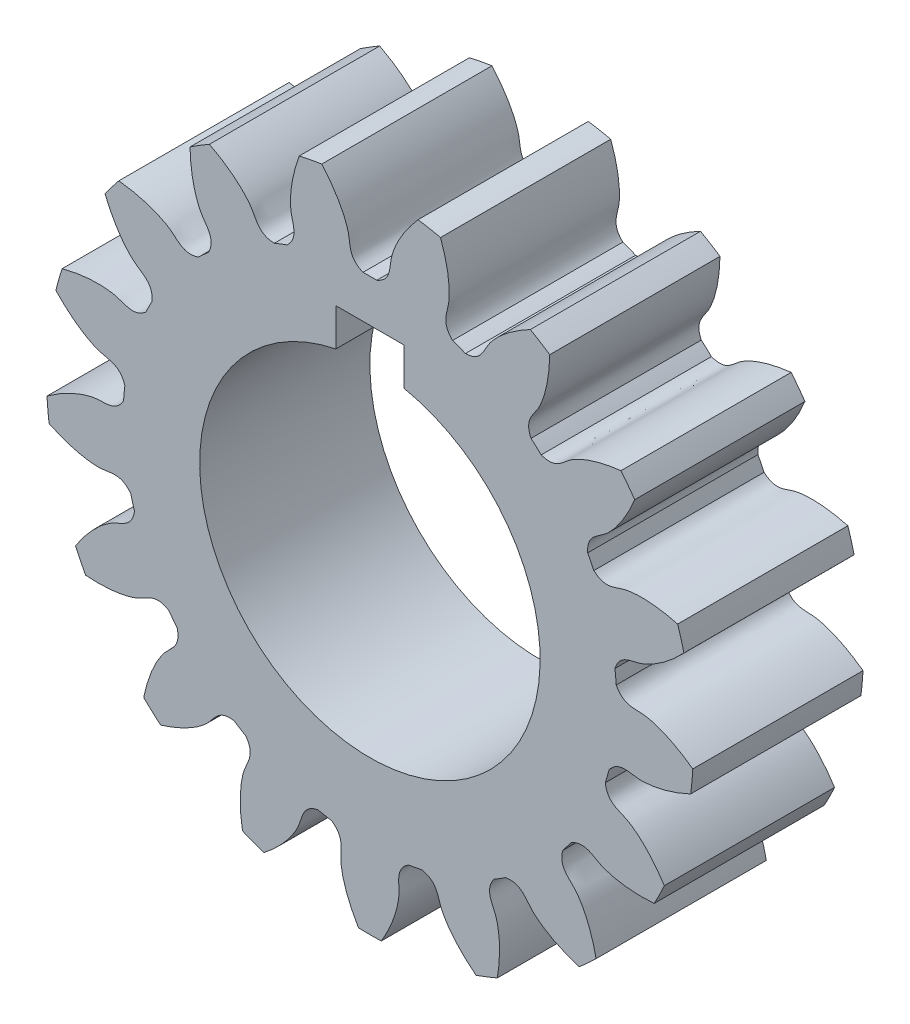
SolidWorks part; units mm, degrees
ref_plane "前视基准面" through (0, 0, 0) normal (0, 0, 1) x (1, 0, 0)
ref_plane "上视基准面" through (0, 0, 0) normal (0, 1, 0) x (1, 0, 0)
ref_plane "右视基准面" through (0, 0, 0) normal (1, 0, 0) x (0, 0, -1)
sketch "草图1" plane through (0, 0, 0) normal (0, 0, 1) x (1, 0, 0)
  circle A0 centre (0, 0) radius 19
extrude "凸台-拉伸1" add sketch "草图1" along normal blind 10
ref_axis "基准轴1" through (0, 0, 10) along (0, 0, -1)
sketch "草图2" plane through (0, 0, 0) normal (0, 0, 1) x (1, 0, 0)
  line L0 (0, 0) -> (0, 19) construction
  circle A0 centre (0, 0) radius 19 construction
  arc A1 (0.4034, 14.4944) -> (-0.4034, 14.4944) centre (0, 0) ccw
  arc A2 (6.2313, 21.4814) -> (-6.2313, 21.4814) centre (0, 0) ccw
  spline S0 degree 3 poles (0.4034, 14.4944) (1.2558, 14.8496) (1.1324, 15.5096) (1.2766, 16.1296) (1.29, 16.1823) (1.306, 16.2408) (1.3251, 16.3052) (1.3474, 16.3752) (1.3731, 16.4508) (1.4025, 16.5319) (1.4359, 16.6184) (1.4733, 16.7101) (1.5152, 16.8068) (1.5616, 16.9086) (1.6128, 17.0151) (1.669, 17.1264) (1.7304, 17.2421) (1.7972, 17.3621) (1.8696, 17.4863) (1.9478, 17.6145) (2.032, 17.7465) (2.1224, 17.8821) (2.2191, 18.0211) (2.3223, 18.1634) (2.4322, 18.3086) (2.5489, 18.4566) (2.6727, 18.6072) (2.8035, 18.7601) (2.9417, 18.9152) (3.0873, 19.0722) (3.2404, 19.2308) (3.4012, 19.3908) (3.5698, 19.552) (3.7462, 19.7141) (3.9307, 19.8769) (4.1233, 20.0401) (4.324, 20.2035) (4.533, 20.3667) (4.7503, 20.5295) (4.9761, 20.6917) (5.2103, 20.853) (5.453, 21.0131) (5.7916, 21.2269) (6.0532, 21.3811) (6.2313, 21.4814) knots 0 0 0 0 0.193883 0.199024 0.204851 0.211363 0.21856 0.226443 0.235011 0.244265 0.254205 0.264829 0.27614 0.288136 0.300817 0.314184 0.328236 0.342973 0.358397 0.374505 0.391299 0.408779 0.426944 0.445795 0.465331 0.485552 0.506459 0.528051 0.550329 0.573293 0.596941 0.621276 0.646296 0.672001 0.698392 0.725468 0.753229 0.781677 0.810809 0.840627 0.871131 0.90232 0.934195 1 1 1 1
  spline S1 degree 3 poles (-0.4034, 14.4944) (-1.2558, 14.8496) (-1.1324, 15.5096) (-1.2766, 16.1296) (-1.29, 16.1823) (-1.306, 16.2408) (-1.3251, 16.3052) (-1.3474, 16.3752) (-1.3731, 16.4508) (-1.4025, 16.5319) (-1.4359, 16.6184) (-1.4733, 16.7101) (-1.5152, 16.8068) (-1.5616, 16.9086) (-1.6128, 17.0151) (-1.669, 17.1264) (-1.7304, 17.2421) (-1.7972, 17.3621) (-1.8696, 17.4863) (-1.9478, 17.6145) (-2.032, 17.7465) (-2.1224, 17.8821) (-2.2191, 18.0211) (-2.3223, 18.1634) (-2.4322, 18.3086) (-2.5489, 18.4566) (-2.6727, 18.6072) (-2.8035, 18.7601) (-2.9417, 18.9152) (-3.0873, 19.0722) (-3.2404, 19.2308) (-3.4012, 19.3908) (-3.5698, 19.552) (-3.7462, 19.7141) (-3.9307, 19.8769) (-4.1233, 20.0401) (-4.324, 20.2035) (-4.533, 20.3667) (-4.7503, 20.5295) (-4.9761, 20.6917) (-5.2103, 20.853) (-5.453, 21.0131) (-5.7916, 21.2269) (-6.0532, 21.3811) (-6.2313, 21.4814) knots 0 0 0 0 0.193883 0.199024 0.204851 0.211363 0.21856 0.226443 0.235011 0.244265 0.254205 0.264829 0.27614 0.288136 0.300817 0.314184 0.328236 0.342973 0.358397 0.374505 0.391299 0.408779 0.426944 0.445795 0.465331 0.485552 0.506459 0.528051 0.550329 0.573293 0.596941 0.621276 0.646296 0.672001 0.698392 0.725468 0.753229 0.781677 0.810809 0.840627 0.871131 0.90232 0.934195 1 1 1 1
extrude "切除-拉伸1" cut sketch "草图2" along normal through all
pattern_circular "阵列(圆周)1" count 17 every 21.176 about axis through (0, 0, 10) along (0, 0, -1) of "切除-拉伸1"
sketch "草图3" plane through (0, 0, 0) normal (0, 0, 1) x (1, 0, 0)
  circle A0 centre (0, 0) radius 17 construction
  dimension "Dn" = 34
sketch "草图4" plane through (0, 0, 10) normal (0, 0, 1) x (1, 0, 0)
  line L1 (-2, 12) -> (2, 12)
  line L2 (-2, 12) -> (-2, 9.798)
  line L4 (2, 12) -> (2, 9.798)
  arc A0 (-2, 9.798) -> (2, 9.798) centre (0, 0) ccw
  point P3 (0, 10)
  dimension "D1" = 20
  dimension "D2" = 2
extrude "切除-拉伸2" cut sketch "草图4" against normal through all
